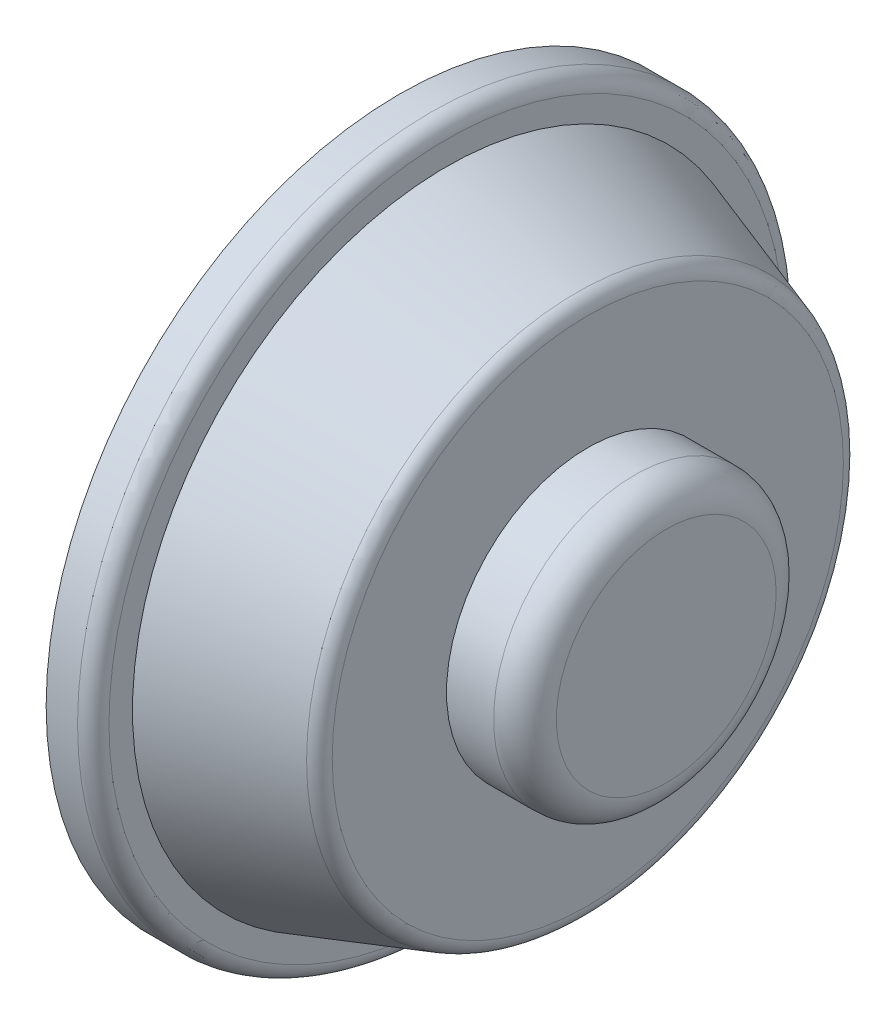
SolidWorks part; units mm, degrees
ref_plane "Front Plane" through (0, 0, 0) normal (0, 0, 1) x (1, 0, 0)
ref_plane "Top Plane" through (0, 0, 0) normal (0, 1, 0) x (1, 0, 0)
ref_plane "Right Plane" through (0, 0, 0) normal (1, 0, 0) x (0, 0, -1)
sketch "Sketch1" plane through (0, 0, 0) normal (1, 0, 0) x (0, 0, -1)
  circle A0 centre (0, 0) radius 22.5
  dimension "D1" = 45
extrude "Boss-Extrude1" add sketch "Sketch1" along normal blind 3
sketch "Sketch2" plane through (3, 0, 0) normal (1, 0, 0) x (0, 0, -1)
  circle A0 centre (0, 0) radius 20
  dimension "D1" = 40
ref_plane "Plane1" through (12, 0, 0) normal (1, 0, 0) x (0, 0, -1)
sketch "Sketch3" plane through (12, 0, 0) normal (1, 0, 0) x (0, 0, -1)
  circle A0 centre (0, 0) radius 17
  dimension "D1" = 34
loft "Loft1" add profiles "Sketch3", "Sketch2" connector at (12, 13.7784, 9.9578) connector at (3, 14.6223, 13.6451)
sketch "Sketch4" plane through (12, 0, 0) normal (1, 0, 0) x (0, 0, -1)
  circle A0 centre (0, 0) radius 9
  dimension "D1" = 18
extrude "Boss-Extrude2" add sketch "Sketch4" along normal blind 5
fillet "Fillet1" radius 2 1 edges at (17, 0, -9)
fillet "Fillet2" radius 1 2 edges at (3, 0, -22.5) (12, 0, -17)
sketch "Sketch5" plane through (0, 0, 0) normal (-1, 0, 0) x (0, 0, 1)
  circle A0 centre (0, 0) radius 21
  dimension "D1" = 42
extrude "Cut-Extrude1" cut sketch "Sketch5" against normal blind 2
sketch "Sketch6" plane through (2, 0, 0) normal (-1, 0, 0) x (0, 0, 1)
  circle A0 centre (0, 0) radius 16
  circle A1 centre (0, 0) radius 21 construction
  circle A2 centre (0, 0) radius 21
  dimension "D1" = 32
extrude "Boss-Extrude3" add sketch "Sketch6" along normal blind 1
fillet "Fillet3" radius 6 1 edges at (1, 0, 16)
